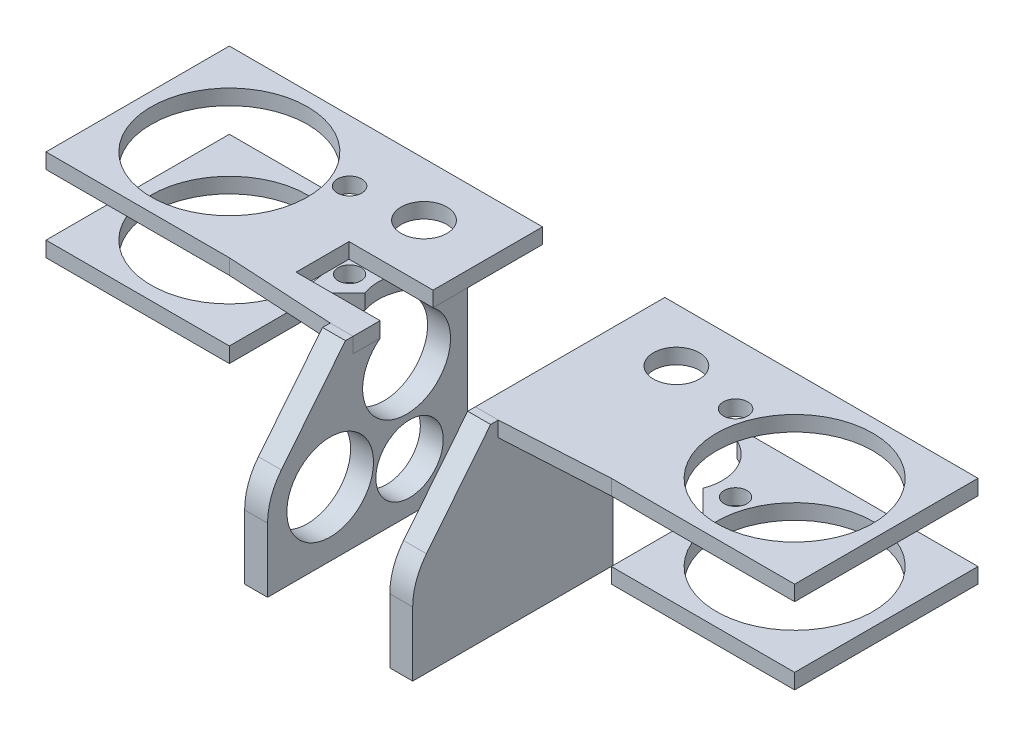
SolidWorks part; units mm, degrees
material "Alum Plate"
ref_plane "Front Plane" through (0, 0, 0) normal (0, 0, 1) x (1, 0, 0)
ref_plane "Top Plane" through (0, 0, 0) normal (0, 1, 0) x (1, 0, 0)
ref_plane "Right Plane" through (0, 0, 0) normal (1, 0, 0) x (0, 0, -1)
sketch "Sketch1" plane through (0, 0, 0) normal (0, 1, 0) x (1, 0, 0)
  line L0 (0, 0) -> (117.475, 0) construction
  line L1 (-117.475, 0) -> (0, 0) construction
  line L3 (-9.525, 165.735) -> (-3.175, 165.735)
  line L4 (-9.525, 165.735) -> (-9.525, 51.435)
  line L5 (-9.525, 51.435) -> (-3.175, 51.435)
  line L6 (-3.175, 165.735) -> (-3.175, 51.435)
  line L7 (-9.525, 165.735) -> (-3.175, 51.435) construction
  line L8 (-9.525, 51.435) -> (-3.175, 165.735) construction
  line L14 (-155.575, -76.2) -> (155.575, -76.2)
  line L18 (-117.475, 0) -> (-52.4506, 15.875) construction
  line L19 (52.4506, 15.875) -> (117.475, 0) construction
  line L20 (-25.4, 38.1) -> (0, 38.1) construction
  line L21 (-6.35, 108.585) -> (0, 108.585)
  line L29 (0, 0) -> (0, -18.415) construction
  line L30 (-117.475, 0) -> (-80.2096, 12.7) construction
  line L43 (-80.2096, 12.7) -> (-52.4506, 15.875) construction
  line L44 (52.4506, 15.875) -> (80.2096, 12.7) construction
  line L55 (80.2096, 12.7) -> (117.475, 0) construction
  line L69 (-155.575, -76.2) -> (-155.575, 38.1)
  line L70 (-155.575, 38.1) -> (155.575, 38.1)
  line L71 (155.575, -76.2) -> (155.575, 38.1)
  line L78 (0, 108.585) -> (0, -18.415)
  line L79 (0, -18.415) -> (0, -145.415) construction
  line L80 (-9.525, -202.565) -> (-3.175, -202.565) construction
  line L81 (-9.525, -202.565) -> (-9.525, -88.265) construction
  line L82 (-9.525, -88.265) -> (-3.175, -88.265) construction
  line L83 (-3.175, -202.565) -> (-3.175, -88.265) construction
  line L84 (-9.525, -202.565) -> (-3.175, -88.265) construction
  line L85 (-9.525, -88.265) -> (-3.175, -202.565) construction
  line L86 (0, -145.415) -> (-6.35, -145.415) construction
  line L87 (-34.925, -76.2) -> (-25.4, -76.2)
  line L88 (-34.925, -76.2) -> (-34.925, 38.1)
  line L89 (-34.925, 38.1) -> (-25.4, 38.1)
  line L90 (-25.4, -76.2) -> (-25.4, 38.1)
  line L91 (34.925, -76.2) -> (25.4, -76.2)
  line L92 (34.925, -76.2) -> (34.925, 38.1)
  line L93 (34.925, 38.1) -> (25.4, 38.1)
  line L94 (25.4, -76.2) -> (25.4, 38.1)
  line L95 (0, 38.1) -> (25.4, 38.1) construction
  circle A0 centre (-117.475, 0) radius 32.5
  circle A1 centre (-117.475, 0) radius 25
  circle A2 centre (117.475, 0) radius 32.5
  circle A3 centre (117.475, 0) radius 25
  circle A4 centre (-52.4506, 15.875) radius 17.5006
  circle A5 centre (52.4506, 15.875) radius 17.5006
  circle A6 centre (-80.2096, 12.7) radius 22.86
  circle A7 centre (80.2096, 12.7) radius 22.86
  point P8 (-6.35, 108.585)
  point P21 (117.475, 32.5)
  point P25 (52.4506, 33.3756)
  point P29 (52.4506, -1.6256)
  point P31 (0, -76.2)
  point P32 (-6.35, -145.415)
  point P62 (149.975, 0)
  dimension "D1" = 50
  dimension "D2" = 65
  dimension "D8" = 35.0012
  dimension "D11" = 127
  dimension "D12" = 56.515
  dimension "D17" = 45.72
  dimension "D3" = 114.3
  dimension "D4" = 6.35
  dimension "D5" = 234.95
  dimension "D6" = 38.1
  dimension "D7" = 38.1
  dimension "D9" = 114.3
  dimension "D10" = 9.525
  dimension "D13" = 9.525
  dimension "D14" = 50.8
  dimension "D15" = 27.94
  dimension "D16" = 39.37
  dimension "D18" = 22.225
  dimension "D19" = 25.4
sketch "Sketch2" plane through (0, 0, 0) normal (1, 0, 0) x (0, 0, -1)
  line L0 (0, 25.4) -> (0, 56.175) construction
  line L1 (-32.5, 59.675) -> (32.5, 59.675)
  line L2 (-32.5, 59.675) -> (-32.5, 52.675)
  line L3 (-32.5, 52.675) -> (32.5, 52.675)
  line L4 (32.5, 59.675) -> (32.5, 52.675)
  line L5 (-32.5, 59.675) -> (32.5, 52.675) construction
  line L6 (-32.5, 52.675) -> (32.5, 59.675) construction
  line L7 (-32.5, 88.9) -> (32.5, 88.9)
  line L8 (-32.5, 88.9) -> (-32.5, 81.9)
  line L9 (-32.5, 81.9) -> (32.5, 81.9)
  line L10 (32.5, 88.9) -> (32.5, 81.9)
  line L11 (-32.5, 88.9) -> (32.5, 81.9) construction
  line L12 (-32.5, 81.9) -> (32.5, 88.9) construction
  line L13 (-25.8191, 0) -> (33.9817, 0) construction
  line L14 (-18.415, 69.85) -> (-145.415, 69.85)
  line L15 (-76.2, 90.775) -> (38.1, 90.775)
  line L16 (-76.2, 90.775) -> (-76.2, 52.675)
  line L17 (-76.2, 52.675) -> (38.1, 52.675)
  line L18 (38.1, 90.775) -> (38.1, 52.675)
  line L19 (-17.175, 34.947) -> (-50.165, 41.275) construction
  line L20 (-50.165, 41.275) -> (-18.415, 69.85) construction
  line L21 (108.585, 0) -> (-18.415, 0) construction
  line L22 (-76.2, 84.425) -> (38.1, 84.425)
  line L23 (-76.2, 59.025) -> (38.1, 59.025)
  line L24 (-17.175, 34.947) -> (-18.415, 69.85) construction
  line L25 (-3.175, 34.947) -> (-3.175, 81.9) construction
  line L26 (-18.415, 69.85) -> (108.585, 69.85)
  line L32 (-76.2, 14.575) -> (38.1, 14.575)
  line L33 (-76.2, 14.575) -> (-76.2, 11.4)
  line L38 (-76.2, 11.4) -> (38.1, 11.4)
  line L39 (38.1, 14.575) -> (38.1, 11.4)
  line L40 (-1.6256, 39.9242) -> (33.3756, 39.9242)
  line L41 (-1.6256, 39.9242) -> (-1.6256, 84.425)
  line L42 (-1.6256, 84.425) -> (33.3756, 84.425)
  line L43 (33.3756, 39.9242) -> (33.3756, 84.425)
  line L44 (-1.6256, 39.9242) -> (33.3756, 84.425) construction
  line L45 (-1.6256, 84.425) -> (33.3756, 39.9242) construction
  line L46 (-38.1, 90.775) -> (-38.1, 52.675)
  line L47 (-38.1, 71.725) -> (0, 71.725) construction
  line L48 (0, 71.725) -> (38.1, 71.725) construction
  line L49 (-76.2, 14.575) -> (38.1, 11.4) construction
  line L50 (-76.2, 11.4) -> (38.1, 14.575) construction
  circle A0 centre (0, 25.4) radius 25.4
  circle A1 centre (-18.415, 69.85) radius 18.0086
  circle A2 centre (-17.175, 34.947) radius 14
  circle A3 centre (-145.415, 69.85) radius 57.15
  circle A4 centre (-18.415, 69.85) radius 4.7625
  circle A5 centre (-50.165, 41.275) radius 18
  circle A6 centre (108.585, 69.85) radius 57.15
  point P2 (0, 56.175)
  point P8 (0, 85.4)
  point P16 (-32.165, 41.275)
  point P28 (-68.165, 41.275)
  point P32 (15.875, 62.1746)
  point P34 (-202.565, 69.85)
  point P35 (-31.175, 34.947)
  point P36 (-3.175, 34.947)
  point P37 (-0.4064, 69.85)
  point P38 (-36.4236, 69.85)
  point P47 (0, 50.8)
  point P57 (-19.05, 12.9875)
  point P66 (-17.175, 37.6022)
  dimension "D1" = 50.8
  dimension "D8" = 36.0172
  dimension "D2" = 28
  dimension "D11" = 9.525
  dimension "D12" = 36
  dimension "D3" = 7
  dimension "D4" = 38.1
  dimension "D5" = 22.225
  dimension "D6" = 6.35
  dimension "D7" = 6.35
  dimension "D9" = 69.85
  dimension "D10" = 44.5008
  dimension "D13" = 19.05
  dimension "D14" = 31.75
  dimension "D15" = 3.175
  dimension "D16" = 25.4
  dimension "D17" = 34.925
  dimension "D18" = 38.1
  dimension "D19" = 28.575
sketch "Sketch5" plane through (0, 0, 0) normal (0, 1, 0) x (1, 0, 0)
  line L0 (-34.925, -76.2) -> (-34.925, 38.1) construction
  line L1 (-60.071, -3.175) -> (-28.575, -3.175)
  line L2 (-60.071, -3.175) -> (-60.071, -31.175)
  line L3 (-60.071, -31.175) -> (-28.575, -31.175)
  line L4 (-28.575, -3.175) -> (-28.575, -31.175)
  line L5 (-60.071, -3.175) -> (-28.575, -31.175) construction
  line L6 (-60.071, -31.175) -> (-28.575, -3.175) construction
  line L7 (-74.93, -32.165) -> (-34.925, -32.165)
  line L8 (-74.93, -32.165) -> (-74.93, -68.165)
  line L9 (-74.93, -68.165) -> (-34.925, -68.165)
  line L10 (-34.925, -32.165) -> (-34.925, -68.165)
  line L11 (-74.93, -32.165) -> (-34.925, -68.165) construction
  line L12 (-74.93, -68.165) -> (-34.925, -32.165) construction
  line L13 (-60.071, -0.4064) -> (-20.066, -0.4064)
  line L14 (-60.071, -0.4064) -> (-60.071, -36.4236)
  line L15 (-60.071, -36.4236) -> (-20.066, -36.4236)
  line L16 (-20.066, -0.4064) -> (-20.066, -36.4236)
  line L17 (-60.071, -0.4064) -> (-20.066, -36.4236) construction
  line L18 (-60.071, -36.4236) -> (-20.066, -0.4064) construction
  line L20 (-25.4, -76.2) -> (-25.4, 38.1) construction
  point P0 (-44.323, -17.175)
  point P5 (-54.9275, -50.165)
  point P10 (-40.0685, -18.415)
  dimension "D1" = 3.175
  dimension "D2" = 31.496
  dimension "D5" = 40.005
  dimension "D6" = 40.005
ref_plane "Plane1" through (0, 84.425, 0) normal (0, 1, 0) x (1, 0, 0)
ref_plane "Plane2" through (0, 59.025, 0) normal (0, -1, 0) x (-1, 0, 0)
ref_plane "Plane3" through (25.4, 0, 0) normal (1, 0, 0) x (0, 0, -1)
sketch "Sketch6" plane through (25.4, 0, 0) normal (1, 0, 0) x (0, 0, -1)
  line L2 (-70.4677, 57.5729) -> (-43.815, 90.775)
  line L3 (-76.2, 90.775) -> (38.1, 90.775) construction
  line L4 (-43.815, 90.775) -> (-40.64, 90.775)
  line L5 (-40.64, 90.775) -> (-40.64, 84.425)
  line L6 (-76.2, 84.425) -> (38.1, 84.425) construction
  line L7 (-40.64, 84.425) -> (6.985, 84.425)
  line L8 (6.985, 84.425) -> (6.985, 14.575)
  line L10 (-76.2, 14.575) -> (38.1, 14.575) construction
  line L11 (-76.2, 14.575) -> (-76.2, 41.275)
  line L12 (-76.2, 14.575) -> (6.985, 14.575)
  arc A3 (-76.2, 41.275) -> (-70.4677, 57.5729) centre (-50.165, 41.275) cw
  dimension "D1" = 25.4
  dimension "D2" = 22.225
  dimension "D3" = 3.175
extrude "Boss-Extrude1" add sketch "Sketch6" along normal up to vertex (9.525 mm away) up to point (34.925, 0, -38.1)
sketch "Sketch7" plane through (0, 84.425, 0) normal (0, 1, 0) x (1, 0, 0)
  line L0 (25.4, -40.64) -> (34.925, -40.64)
  line L2 (155.575, -76.2) -> (155.575, 38.1) construction
  line L3 (155.575, -38.1) -> (155.575, 38.1)
  line L4 (155.575, 38.1) -> (25.4, 38.1)
  line L5 (25.4, 38.1) -> (25.4, -40.64)
  line L6 (155.575, -38.1) -> (79.375, -38.1)
  line L7 (79.375, -38.1) -> (34.925, -40.64)
  line L8 (117.475, 38.1) -> (117.475, 0) construction
  line L9 (117.475, 0) -> (117.475, -38.1) construction
  circle A0 centre (117.475, 0) radius 32.5 construction
  circle A1 centre (117.475, 0) radius 32.5
  circle A2 centre (80.2096, 12.7) radius 5.08
  circle A3 centre (52.4506, 15.875) radius 9.525
  dimension "D1" = 10.16
  dimension "D2" = 19.05
extrude "Boss-Extrude2" add sketch "Sketch7" along normal up to surface (6.35 mm away) separate body up to face at (30.1625, 90.775, 42.2275)
sketch "Sketch8" plane through (0, 59.025, 0) normal (0, -1, 0) x (-1, 0, 0)
  line L0 (-60.325, 33.2214) -> (-60.325, 38.1)
  line L1 (-79.375, -38.1) -> (-155.575, -38.1)
  line L2 (-79.375, -38.1) -> (-79.375, 38.1) construction
  line L3 (-79.375, 38.1) -> (-155.575, 38.1)
  line L4 (-155.575, -38.1) -> (-155.575, 38.1)
  line L5 (-79.375, -38.1) -> (-155.575, 38.1) construction
  line L6 (-79.375, 38.1) -> (-155.575, -38.1) construction
  line L7 (155.575, 38.1) -> (-155.575, 38.1) construction
  line L8 (-60.325, 38.1) -> (-79.375, 38.1)
  line L9 (-79.375, -38.1) -> (-79.375, 0)
  line L10 (-79.375, 0) -> (-70.2606, 9.1144)
  line L11 (-34.925, -76.2) -> (-34.925, 38.1) construction
  circle A0 centre (-117.475, 0) radius 32.5 construction
  circle A1 centre (-117.475, 0) radius 32.5
  arc A2 (-70.2606, 9.1144) -> (-60.325, 33.2214) centre (-52.4506, 15.875) cw
  circle A3 centre (-80.2096, 12.7) radius 4.7625
  dimension "D1" = 9.525
  dimension "D2" = 19.05
  dimension "D3" = 25.4
  dimension "D4" = 45
  dimension "D5" = 38.1
extrude "Boss-Extrude3" add sketch "Sketch8" along normal up to vertex (6.35 mm away) separate body up to point (0, 52.675, -38.1)
mirror "Mirror2" about plane through (0, 0, 0) normal (1, 0, 0) of bodies 106 108 111
sketch "Sketch10" plane through (-25.4, 0, 0) normal (1, 0, 0) x (0, 0, -1)
  circle A0 centre (-50.165, 41.275) radius 18 construction
  circle A1 centre (-50.165, 41.275) radius 18
  circle A2 centre (-17.175, 34.947) radius 14 construction
  circle A3 centre (-17.175, 34.947) radius 14
extrude "Cut-Extrude2" cut sketch "Sketch10" against normal through all
sketch "Sketch11" plane through (-34.925, 0, 0) normal (-1, 0, 0) x (0, 0, 1)
  circle A1 centre (18.415, 69.85) radius 18.2626
  circle A4 centre (18.415, 69.85) radius 18.0086 construction
  dimension "D1" = 0.254
extrude "Cut-Extrude6" cut sketch "Sketch11" against normal through all
sketch "Sketch12" plane through (0, 84.425, 0) normal (0, -1, 0) x (1, 0, 0)
  line L0 (-60.071, 0.4064) -> (-60.071, 36.4236) construction
  line L1 (-25.4, 7.4108) -> (-60.325, 7.4108)
  line L2 (-25.4, 7.4108) -> (-25.4, 29.4192)
  line L3 (-25.4, 29.4192) -> (-60.325, 29.4192)
  line L4 (-60.325, 7.4108) -> (-60.325, 29.4192)
  line L5 (-25.4, 7.4108) -> (-60.325, 29.4192) construction
  line L6 (-25.4, 29.4192) -> (-60.325, 7.4108) construction
  line L7 (-25.4, -38.1) -> (-25.4, 40.64) construction
  point P4 (-42.8625, 18.415)
  dimension "D1" = 0.254
extrude "Cut-Extrude7" cut sketch "Sketch12" against normal through all
